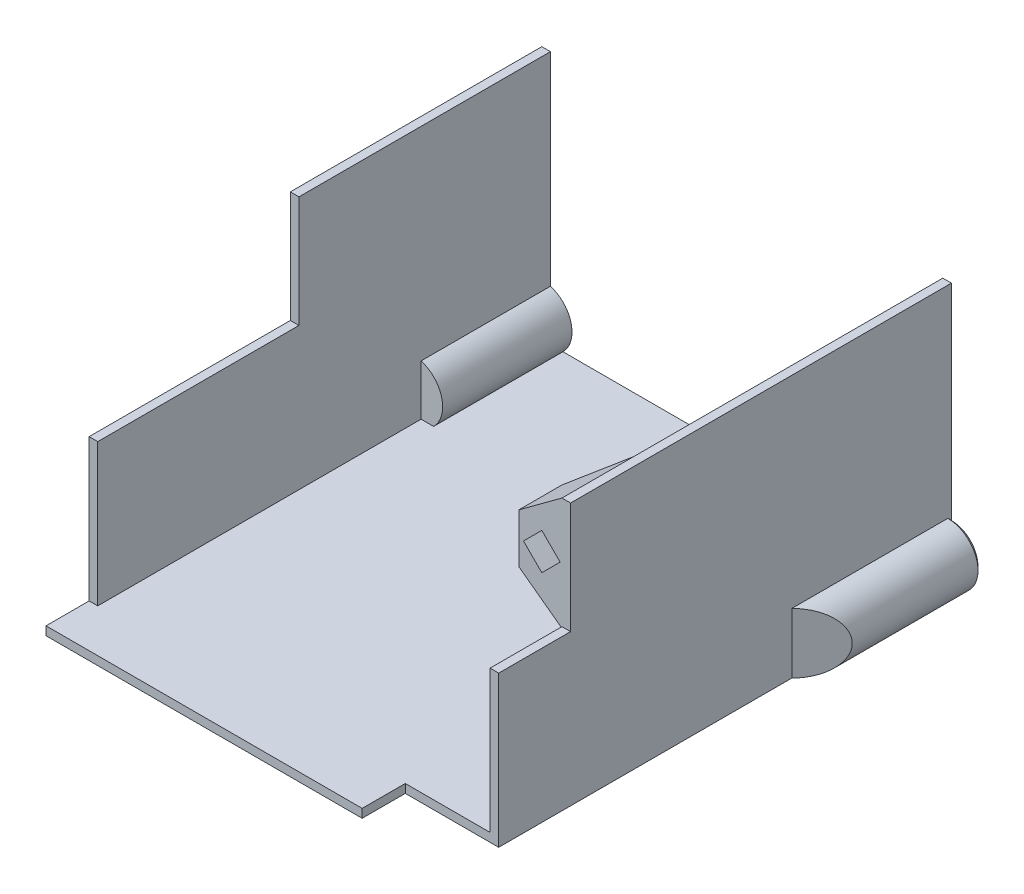
SolidWorks part; units mm, degrees
material "Custom Plastic"
ref_plane "Front Plane" through (0, 0, 0) normal (0, 0, 1) x (1, 0, 0)
ref_plane "Top Plane" through (0, 0, 0) normal (0, 1, 0) x (1, 0, 0)
ref_plane "Right Plane" through (0, 0, 0) normal (1, 0, 0) x (0, 0, -1)
sketch "Sketch1" plane through (0, 0, 0) normal (0, 0, 1) x (1, 0, 0)
  line L1 (-33.6475, 15.5475) -> (-34.8475, 15.5475)
  line L2 (-33.6475, -19.7525) -> (-33.6475, -20.9525) construction
  line L3 (-31.9081, -19.7525) -> (19.2131, -19.7525)
  line L4 (20.9525, 15.5475) -> (20.9525, -12.7276)
  line L5 (-33.6475, -12.7276) -> (-33.6475, 15.5475)
  line L7 (20.9525, 15.5475) -> (22.1525, 15.5475)
  line L8 (-34.8475, 15.5475) -> (-34.8475, -12.5525)
  line L9 (-34.8475, -20.9525) -> (22.1525, -20.9525)
  line L10 (22.1525, 15.5475) -> (22.1525, -12.5525)
  arc A0 (22.1525, -20.9525) -> (22.1525, -12.5525) centre (22.1525, -16.7525) ccw
  circle A1 centre (22.1525, -16.7525) radius 1.6 construction
  arc A2 (20.9525, -12.7276) -> (19.2131, -19.7525) centre (22.1525, -16.7525) ccw
  circle A3 centre (-34.8475, -16.7525) radius 1.6 construction
  arc A4 (-34.8475, -12.5525) -> (-34.8475, -20.9525) centre (-34.8475, -16.7525) ccw
  arc A6 (-31.9081, -19.7525) -> (-33.6475, -12.7276) centre (-34.8475, -16.7525) ccw
  dimension "D2" = 3.2
  dimension "D5" = 4.2
  dimension "D1" = 1.2
  dimension "D3" = 57
  dimension "D4" = 36.5
extrude "Boss-Extrude1" add sketch "Sketch1" along normal blind 69
sketch "Sketch2" plane through (0, 0, 69) normal (0, 0, 1) x (1, 0, 0)
  line L0 (-34.8475, -20.9525) -> (22.1525, -20.9525) construction
  line L1 (9.1525, -20.9525) -> (32.8781, -20.9525)
  line L2 (9.1525, -20.9525) -> (9.1525, -19.7525)
  line L3 (-34.8475, 12.6741) -> (32.8781, 12.6741)
  line L4 (32.8781, -20.9525) -> (32.8781, 12.6741)
  line L5 (22.1525, -12.5525) -> (22.1525, 15.5475) construction
  line L6 (9.1525, -19.7525) -> (-34.8475, -19.7525)
  line L7 (19.2131, -19.7525) -> (-31.9081, -19.7525) construction
  line L8 (-34.8475, 15.5475) -> (-34.8475, -12.5525) construction
  line L9 (-34.8475, -20.9525) -> (-34.8475, -19.7525)
  line L10 (-34.8475, -20.9525) -> (-42.7406, -20.9525)
  line L11 (-34.8475, -20.9525) -> (22.1525, -20.9525) construction
  line L12 (-42.7406, -20.9525) -> (-42.7406, -7.5075)
  line L13 (-42.7406, -7.5075) -> (-34.8475, -7.5075)
  line L14 (-34.8475, -7.5075) -> (-34.8475, 12.6741)
  dimension "D1" = 13
extrude "Cut-Extrude1" cut sketch "Sketch2" against normal blind 6
sketch "Sketch3" plane through (0, 0, 63) normal (0, 0, 1) x (1, 0, 0)
  line L0 (22.1525, -12.5525) -> (22.1525, 12.6741) construction
  line L1 (-34.8475, 15.5475) -> (22.1525, 15.5475)
  line L2 (-34.8475, 15.5475) -> (-34.8475, 0.0475)
  line L3 (-34.8475, 0.0475) -> (22.1525, 0.0475)
  line L4 (22.1525, 15.5475) -> (22.1525, 0.0475)
  dimension "D1" = 15.5
extrude "Cut-Extrude2" cut sketch "Sketch3" against normal blind 10 and the other way blind 10
sketch "Sketch4" plane through (0, 0, 53) normal (0, 0, 1) x (1, 0, 0)
  line L1 (-34.8475, 15.5475) -> (-33.6475, 15.5475)
  line L2 (-34.8475, 15.5475) -> (-34.8475, 0.0475)
  line L3 (-34.8475, 0.0475) -> (-33.6475, 0.0475)
  line L4 (-33.6475, 15.5475) -> (-33.6475, 0.0475)
extrude "Cut-Extrude3" cut sketch "Sketch4" against normal blind 18
sketch "Sketch6" plane through (0, 0, 0) normal (0, 0, -1) x (-1, 0, 0)
  circle A0 centre (-22.1525, -16.7525) radius 1.6
  circle A1 centre (34.8475, -16.7525) radius 1.6
  arc A2 (34.8475, -20.9525) -> (34.8475, -12.5525) centre (34.8475, -16.7525) ccw construction
  arc A3 (-22.1525, -12.5525) -> (-22.1525, -20.9525) centre (-22.1525, -16.7525) ccw construction
  dimension "D1" = 3.2
extrude "Cut-Extrude4" cut sketch "Sketch6" against normal blind 16
sketch "Sketch7" plane through (0, 0, 63) normal (0, 0, 1) x (1, 0, 0)
  line L0 (19.2131, -19.7525) -> (9.1525, -19.7525) construction
  line L1 (22.1525, -12.5525) -> (31.8181, -12.5525)
  line L2 (22.1525, -12.5525) -> (22.1525, -20.9525)
  line L3 (22.1525, -20.9525) -> (31.8181, -20.9525)
  line L4 (31.8181, -12.5525) -> (31.8181, -20.9525)
  line L5 (20.9525, -12.7276) -> (15.0843, -12.7276)
  line L6 (20.9525, -12.7276) -> (20.9525, -19.7525)
  line L7 (20.9525, -19.7525) -> (15.0843, -19.7525)
  line L8 (15.0843, -12.7276) -> (15.0843, -19.7525)
  line L9 (-33.6475, -12.7276) -> (-33.6475, 0.0475) construction
  line L10 (-34.8475, -20.9525) -> (-44.0251, -20.9525)
  line L11 (-34.8475, -20.9525) -> (-34.8475, -7.6032)
  line L12 (-34.8475, -7.6032) -> (-44.0251, -7.6032)
  line L13 (-44.0251, -20.9525) -> (-44.0251, -7.6032)
  line L14 (-33.6475, -7.6032) -> (-26.816, -7.6032)
  line L15 (-33.6475, -7.6032) -> (-33.6475, -19.7525)
  line L16 (-33.6475, -19.7525) -> (-26.816, -19.7525)
  line L17 (-26.816, -7.6032) -> (-26.816, -19.7525)
  line L18 (9.1525, -19.7525) -> (-34.8475, -19.7525) construction
extrude "Cut-Extrude5" cut sketch "Sketch7" against normal offset from surface (45 mm away) 18 up to face at (-36.4475, -16.7525, 0)
chamfer "Chamfer1" distance 4.2 angle 45 2 edges at (22.1525, -16.7525, 18) (-34.8475, -16.7525, 18)
chamfer "Chamfer3" distance 0.6 angle 30 2 edges at (20.5525, -16.7525, 0) (-36.4475, -16.7525, 0) first distance on face at (20.5525, -16.7525, 16) first distance on face at (-36.4475, -16.7525, 16)
chamfer "Chamfer4" distance 0.5 angle 45 3 edges at (-39.0475, -16.7525, 0) (-6.3475, -20.9525, 0) (26.3525, -16.7525, 0)
sketch "Sketch8" plane through (0, 0, 53) normal (0, 0, 1) x (1, 0, 0)
  line L0 (18.1525, 9.2975) -> (14.9525, 9.2975) construction
  line L1 (15.6025, 7.6975) -> (18.1525, 10.2475)
  line L2 (14.9525, 6.0975) -> (18.1525, 6.0975) construction
  line L4 (14.9525, 11.1225) -> (14.9525, 9.2975)
  line L5 (14.9525, 6.0975) -> (14.9525, 4.2725)
  line L7 (20.9525, 15.5475) -> (20.9525, 0.0475) construction
  line L8 (20.9525, -0.1525) -> (22.1525, -0.1525)
  line L9 (22.1525, 0.0475) -> (22.1525, 15.5475) construction
  line L10 (22.1525, -0.1525) -> (22.1525, 15.5475)
  line L11 (22.1525, 15.5475) -> (20.9525, 15.5475)
  line L12 (15.6025, 7.6975) -> (18.1525, 5.1475)
  line L13 (18.1525, 10.2475) -> (20.7025, 7.6975)
  line L14 (18.1525, 5.1475) -> (20.7025, 7.6975)
  line L15 (15.6025, 7.6975) -> (20.7025, 7.6975) construction
  line L16 (18.1525, 10.2475) -> (18.1525, 5.1475) construction
  line L17 (14.9525, 9.2975) -> (14.9525, 6.0975)
  line L18 (20.9525, 15.5475) -> (14.9525, 11.1225)
  line L19 (20.9525, -0.1525) -> (14.9525, 4.2725)
  arc A0 (18.1525, 6.0975) -> (18.1525, 9.2975) centre (18.1525, 7.6975) ccw construction
  circle A1 centre (18.1525, 7.6975) radius 2.55 construction
  dimension "D1" = 1.6
  dimension "D5" = 5.1
  dimension "D2" = 2.8
  dimension "D3" = 7.85
  dimension "D4" = 6
  dimension "D6" = 6.85
extrude "Boss-Extrude2" add sketch "Sketch8" against normal blind 10
sketch "Sketch10" plane through (0, 0, 43) normal (0, 0, -1) x (-1, 0, 0)
  line L5 (-18.1525, 10.2475) -> (-18.1525, 5.1475) construction
  arc A0 (-18.1525, 10.6975) -> (-18.1525, 4.6975) centre (-18.1525, 7.6975) ccw
  arc A1 (-18.1525, 4.6975) -> (-18.1525, 10.6975) centre (-18.1525, 7.6975) ccw
  dimension "D1" = 3
extrude "Cut-Extrude6" cut sketch "Sketch10" against normal offset from surface 6 and the other way through all up to face at (19.5811, 6.6332, 53)
sketch "Sketch11" plane through (0, 15.5475, 0) normal (0, 1, 0) x (1, 0, 0)
  line L0 (20.9525, -43) -> (14.9525, -47)
  line L1 (14.9525, -43) -> (14.9525, -53) construction
  line L2 (14.9525, -47) -> (14.9525, -43)
  line L3 (14.9525, -43) -> (20.9525, -43)
extrude "Cut-Extrude7" cut sketch "Sketch11" against normal up to surface (11.275 mm away) up to face at (17.9525, 2.06, 48)
